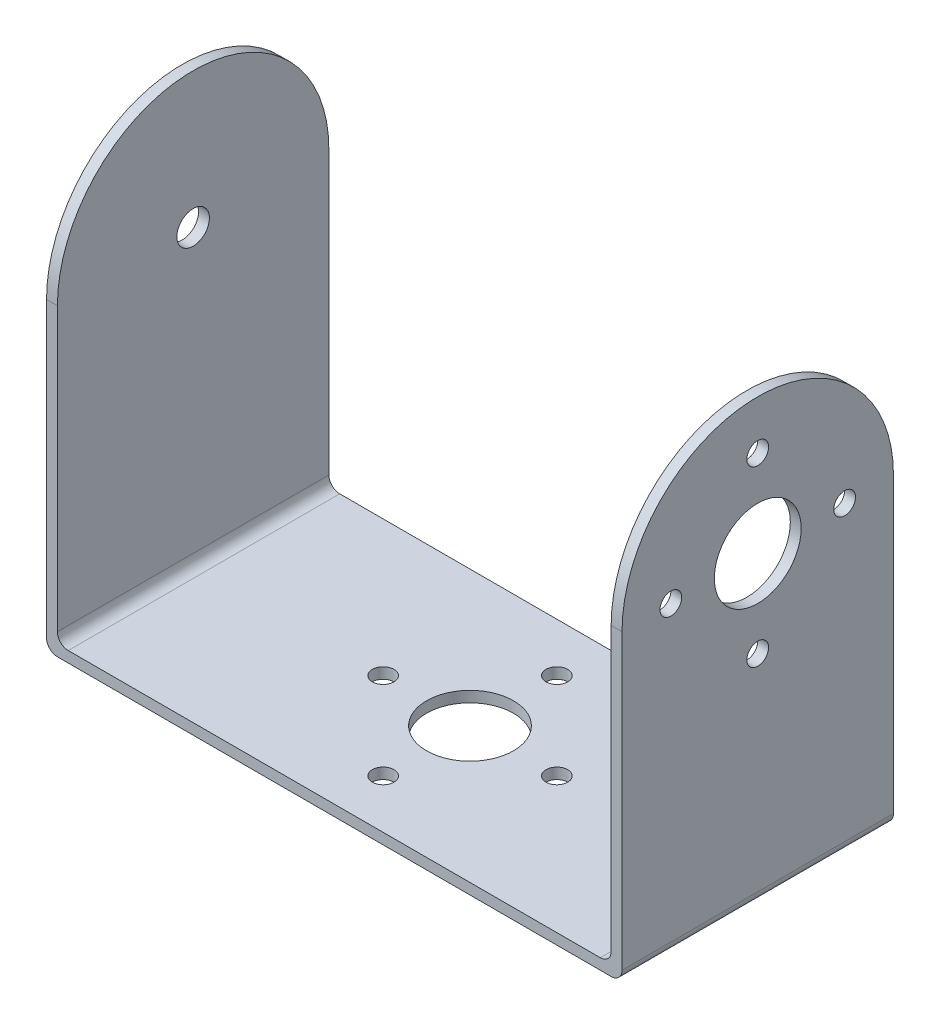
SolidWorks part; units mm, degrees
ref_plane "Front" through (0, 0, 0) normal (0, 0, 1) x (1, 0, 0)
ref_plane "Top" through (0, 0, 0) normal (0, 1, 0) x (1, 0, 0)
ref_plane "Right" through (0, 0, 0) normal (1, 0, 0) x (0, 0, -1)
sketch "Sketch1" plane through (0, 0, 0) normal (0, 0, 1) x (1, 0, 0)
  line L0 (-0.5, 40) -> (0.5, 40)
  line L1 (51.5, 40) -> (52.5, 40)
  line L3 (-0.5, 0.5) -> (-0.5, 40)
  line L4 (0.5, -0.5) -> (51.5, -0.5)
  line L5 (52.5, 0.5) -> (52.5, 40)
  line L6 (0.5, 1.5) -> (0.5, 40)
  line L7 (1.5, 0.5) -> (50.5, 0.5)
  line L8 (51.5, 1.5) -> (51.5, 40)
  arc A0 (50.5, 0.5) -> (51.5, 1.5) centre (50.5, 1.5) ccw
  arc A1 (51.5, -0.5) -> (52.5, 0.5) centre (51.5, 0.5) ccw
  arc A2 (0.5, 1.5) -> (1.5, 0.5) centre (1.5, 1.5) ccw
  arc A3 (-0.5, 0.5) -> (0.5, -0.5) centre (0.5, 0.5) ccw
  dimension "D1" = 1
extrude "Boss-Extrude1" add sketch "Sketch1" against normal blind 25
sketch "Sketch2" plane through (52.5, 0, 0) normal (1, 0, 0) x (0, 0, -1)
  line L3 (0, 27.5) -> (0, 40)
  line L4 (0, 40) -> (25, 40)
  line L5 (25, 40) -> (25, 27.5)
  arc A0 (25, 27.5) -> (0, 27.5) centre (12.5, 27.5) ccw
extrude "Cut-Extrude1" cut sketch "Sketch2" against normal through all contours A0 L4 | A0 region at (52.5, 37.2079, -22.2079) region at (52.5, 37.2079, -2.7921)
sketch "Sketch3" plane through (0, 0.5, 0) normal (0, 1, 0) x (1, 0, 0)
  circle A0 centre (26, 12.5) radius 4
  circle A1 centre (34, 12.5) radius 1
  circle A2 centre (26, 20.5) radius 1
  circle A3 centre (26, 4.5) radius 1
  circle A4 centre (18, 12.5) radius 1
  point P13 (26, 12.5)
  dimension "D1" = 4
extrude "Cut-Extrude2" cut sketch "Sketch3" against normal through all contours A0 | A1 | A2 | A4 | A4 | A3 region at (26, 0.5, -12.5) region at (34, 0.5, -12.5) region at (26, 0.5, -20.5) region at (18, 0.5, -12.5)
sketch "Sketch4" plane through (52.5, 0, 0) normal (1, 0, 0) x (0, 0, -1)
  circle A0 centre (12.5, 27.5) radius 4
  circle A1 centre (20.5, 27.5) radius 1
  circle A2 centre (12.5, 35.5) radius 1
  circle A3 centre (12.5, 19.5) radius 1
  circle A4 centre (4.5, 27.5) radius 1
  point P14 (12.5, 27.5)
extrude "Cut-Extrude3" cut sketch "Sketch4" against normal blind 25
sketch "Sketch5" plane through (-0.5, 0, 0) normal (-1, 0, 0) x (0, 0, 1)
  circle A0 centre (-12.5, 27.5) radius 1.5
extrude "Cut-Extrude4" cut sketch "Sketch5" against normal blind 25 contours A0
